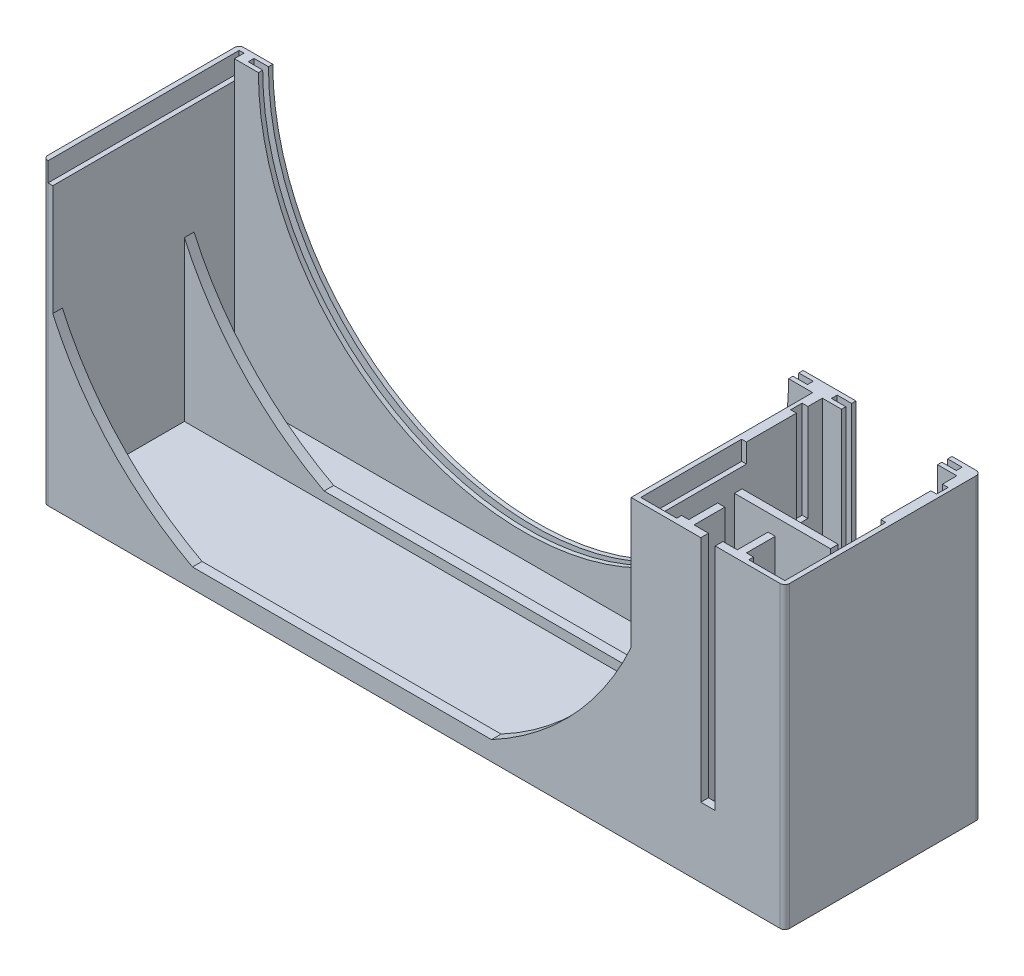
SolidWorks part; units mm, degrees
ref_plane "Plan de face" through (0, 0, 0) normal (0, 0, 1) x (1, 0, 0)
ref_plane "Plan de dessus" through (0, 0, 0) normal (0, 1, 0) x (1, 0, 0)
ref_plane "Plan de droite" through (0, 0, 0) normal (1, 0, 0) x (0, 0, -1)
sketch "Esquisse1" plane through (0, 0, 0) normal (0, 1, 0) x (1, 0, 0)
  line L1 (0, 0) -> (154.4, 0)
  line L2 (0, 0) -> (0, 40.8)
  line L3 (0, 40.8) -> (154.4, 40.8)
  line L4 (154.4, 0) -> (154.4, 40.8)
  dimension "D1" = 154.4
  dimension "D2" = 40.8
extrude "Boss.-Extru.1" add sketch "Esquisse1" along normal blind 2
sketch "Esquisse2" plane through (0, 2, 0) normal (0, 1, 0) x (1, 0, 0)
  line L0 (2, 37.8) -> (2, 29.4)
  line L1 (0, 40.8) -> (154.4, 40.8)
  line L2 (0, 40.8) -> (0, 0)
  line L3 (0, 0) -> (154.4, 0)
  line L4 (154.4, 40.8) -> (154.4, 0)
  line L5 (2, 2) -> (122.4, 2)
  line L8 (124.4, 37.8) -> (124.4, 2)
  line L10 (122.4, 37.8) -> (122.4, 29.4)
  line L22 (152.4, 37.8) -> (152.4, 2)
  line L23 (2, 38.8) -> (152.4, 38.8) construction
  line L24 (124.4, 2) -> (132.4, 2)
  line L25 (152.4, 38.8) -> (152.4, 2) construction
  line L26 (144.4, 2) -> (152.4, 2)
  line L27 (2, 2) -> (152.4, 2) construction
  line L29 (132.4, 2) -> (132.4, 8)
  line L30 (132.4, 8) -> (144.4, 8)
  line L31 (144.4, 2) -> (144.4, 8)
  line L32 (2, 27.4) -> (2, 2)
  line L33 (2, 29.4) -> (122.4, 29.4)
  line L35 (2, 27.4) -> (122.4, 27.4)
  line L37 (122.4, 27.4) -> (122.4, 2)
  line L38 (2, 38.8) -> (2, 2) construction
  line L39 (122.4, 37.8) -> (2, 37.8)
  line L40 (152.4, 37.8) -> (124.4, 37.8)
  dimension "D2" = 2
  dimension "D3" = 120.4
  dimension "D4" = 12
  dimension "D5" = 6
  dimension "D6" = 8
  dimension "D7" = 2
  dimension "D8" = 25.4
  dimension "D9" = 3
  dimension "D11" = 3
  dimension "D1" = 2
extrude "Boss.-Extru.2" add sketch "Esquisse2" along normal blind 60.2
sketch "Esquisse3" plane through (0, 0, 0) normal (0, 0, 1) x (1, 0, 0)
  line L3 (2, 62.2) -> (122.4, 62.2)
  line L4 (2, 62.2) -> (2, 35.1452)
  line L5 (31.0751, 4) -> (93.3249, 4)
  line L6 (122.4, 62.2) -> (122.4, 35.1452)
  line L7 (0, 62.2) -> (0, 0) construction
  line L8 (0, 0) -> (154.4, 0) construction
  line L9 (0, 62.2) -> (154.4, 62.2) construction
  arc A0 (2, 35.1452) -> (31.0751, 4) centre (62.2, 62.2) ccw
  arc A1 (93.3249, 4) -> (122.4, 35.1452) centre (62.2, 62.2) ccw
  dimension "D1" = 132
  dimension "D2" = 2
  dimension "D3" = 4
  dimension "D4" = 120.4
extrude "Enlèv. mat.-Extru.1" cut sketch "Esquisse3" against normal up to surface (29.4 mm away) up to face at (62.2, 32.1, -29.4)
sketch "Esquisse15" plane through (0, 0, -40.8) normal (0, 0, -1) x (-1, 0, 0)
  line L0 (-154.4, 62.2) -> (-122.4, 62.2) construction
  line L1 (-148.4, 62.2) -> (-128.4, 62.2)
  line L2 (-148.4, 62.2) -> (-148.4, 15)
  line L3 (-148.4, 15) -> (-128.4, 15)
  line L4 (-128.4, 62.2) -> (-128.4, 15)
  line L5 (-154.4, 62.2) -> (0, 62.2) construction
  line L6 (-154.4, 62.2) -> (-154.4, 0) construction
  line L7 (-154.4, 0) -> (0, 0) construction
  point P9 (-138.4, 62.2)
  point P10 (-138.4, 62.2)
  dimension "D1" = 32
  dimension "D2" = 6
  dimension "D3" = 15
sketch "Esquisse4" plane through (0, 62.2, 0) normal (0, 1, 0) x (1, 0, 0)
  line L0 (2, 0) -> (1, 0)
  line L10 (130.9, 1) -> (130.9, 2)
  line L12 (124.4, 2) -> (124.4, 22)
  line L13 (124.4, 22) -> (123.4, 22)
  line L14 (123.4, 2) -> (123.4, 22)
  line L16 (152.4, 2) -> (152.4, 22)
  line L17 (152.4, 22) -> (153.4, 22)
  line L18 (153.4, 2) -> (153.4, 22)
  line L19 (124.4, 2) -> (130.9, 2)
  line L20 (123.4, 2) -> (123.4, 1)
  line L21 (123.4, 1) -> (130.9, 1)
  line L22 (153.4, 2) -> (153.4, 1)
  line L23 (130.9, 1.5) -> (145.9, 1.5) construction
  line L24 (145.9, 1) -> (145.9, 2)
  line L25 (145.9, 2) -> (152.4, 2)
  line L26 (145.9, 1) -> (153.4, 1)
  line L27 (152.4, 2) -> (152.4, 37.8) construction
  line L28 (0, 0) -> (2, 0) construction
  line L29 (1, 0) -> (1, 39.8)
  line L31 (2, 39.8) -> (1, 39.8)
  line L33 (154.4, 40.8) -> (0, 40.8) construction
  line L38 (2, 39.8) -> (2, 0)
  point P29 (145.9, 1.5)
  dimension "D1" = 1
  dimension "D2" = 1
  dimension "D5" = 1
  dimension "D6" = 21
  dimension "D8" = 15
  dimension "D9" = 7.5
extrude "Enlèv. mat.-Extru.2" cut sketch "Esquisse4" against normal blind 4
sketch "Esquisse5" plane through (0, 62.2, 0) normal (0, 1, 0) x (1, 0, 0)
  line L0 (124.4, 37.8) -> (124.4, 22) construction
  line L1 (124.4, 32.4) -> (123.2, 32.4)
  line L2 (124.4, 32.4) -> (124.4, 34.8)
  line L3 (124.4, 34.8) -> (123.2, 34.8)
  line L4 (123.2, 32.4) -> (123.2, 34.8)
  line L5 (152.4, 37.8) -> (124.4, 37.8) construction
  line L6 (153.6, 32.4) -> (153.6, 34.8)
  line L13 (124.4, 37.8) -> (152.4, 37.8) construction
  line L15 (152.4, 22) -> (152.4, 37.8) construction
  line L16 (138.4, 37.8) -> (138.4, 0) construction
  line L17 (122.4, 0) -> (154.4, 0) construction
  line L18 (152.4, 34.8) -> (153.6, 34.8)
  line L19 (152.4, 32.4) -> (152.4, 34.8)
  line L20 (152.4, 32.4) -> (153.6, 32.4)
  dimension "D1" = 3
  dimension "D2" = 2.4
  dimension "D3" = 1.2
extrude "Enlèv. mat.-Extru.3" cut sketch "Esquisse5" against normal offset from surface (20.2 mm away) 40 up to face at (138.4, 2, -12.45)
sketch "Esquisse6" plane through (0, 2, 0) normal (0, 1, 0) x (1, 0, 0)
  line L11 (152.4, 37.8) -> (133, 37.8)
  line L12 (152.4, 37.8) -> (152.4, 22.4)
  line L13 (152.4, 22.4) -> (133, 22.4)
  line L14 (133, 37.8) -> (133, 22.4)
  line L15 (152.4, 37.8) -> (131.8, 37.8)
  line L16 (152.4, 37.8) -> (152.4, 21.2)
  line L17 (152.4, 21.2) -> (131.8, 21.2)
  line L18 (131.8, 37.8) -> (131.8, 21.2)
  dimension "D1" = 15.4
  dimension "D2" = 19.4
  dimension "D3" = 1.2
  dimension "D4" = 1.2
extrude "Boss.-Extru.3" add sketch "Esquisse6" along normal blind 8
sketch "Esquisse9" plane through (0, 0, -8) normal (0, 0, -1) x (-1, 0, 0)
  line L0 (-132.4, 2) -> (-144.4, 2) construction
  line L1 (-133.9, 62.2) -> (-142.9, 62.2)
  line L2 (-133.9, 62.2) -> (-133.9, 10.5)
  line L3 (-133.9, 10.5) -> (-142.9, 10.5)
  line L4 (-142.9, 62.2) -> (-142.9, 10.5)
  line L5 (-132.4, 62.2) -> (-144.4, 62.2) construction
  line L6 (-132.4, 2) -> (-144.4, 2) construction
  point P12 (-138.4, 10.5)
  point P13 (-138.4, 2)
  dimension "D1" = 8.5
  dimension "D2" = 9
extrude "Enlèv. mat.-Extru.5" cut sketch "Esquisse9" against normal blind 6.4
sketch "Esquisse10" plane through (0, 0, -1.6) normal (0, 0, -1) x (-1, 0, 0)
  line L0 (-142.9, 10.5) -> (-133.9, 10.5) construction
  line L1 (-136.9, 62.2) -> (-139.9, 62.2)
  line L2 (-136.9, 62.2) -> (-136.9, 14.5)
  line L3 (-136.9, 14.5) -> (-139.9, 14.5)
  line L4 (-139.9, 62.2) -> (-139.9, 14.5)
  line L5 (-133.9, 62.2) -> (-142.9, 62.2) construction
  line L6 (-133.9, 62.2) -> (-142.9, 62.2) construction
  point P12 (-138.4, 62.2)
  point P13 (-138.4, 14.5)
  dimension "D1" = 3
  dimension "D2" = 4
extrude "Enlèv. mat.-Extru.6" cut sketch "Esquisse10" against normal through all
sketch "Esquisse11" plane through (0, 2, 0) normal (0, 1, 0) x (1, 0, 0)
  line L0 (132.4, 8) -> (144.4, 8) construction
  line L1 (132.4, 13.1) -> (152.4, 13.1)
  line L2 (132.4, 13.1) -> (132.4, 11.5)
  line L3 (132.4, 11.5) -> (152.4, 11.5)
  line L4 (152.4, 13.1) -> (152.4, 11.5)
  line L5 (132.4, 2) -> (132.4, 8) construction
  line L6 (152.4, 2) -> (152.4, 21.2) construction
  dimension "D1" = 3.5
  dimension "D2" = 1.6
extrude "Boss.-Extru.4" add sketch "Esquisse11" along normal up to surface (60.2 mm away) up to face at (118.7714, 62.2, -17.1333)
sketch "Esquisse12" plane through (0, 0, -40.8) normal (0, 0, -1) x (-1, 0, 0)
  line L0 (-154.4, 62.2) -> (0, 62.2) construction
  line L1 (-124.4, 62.2) -> (0, 62.2) construction
  circle A0 centre (-62.2, 62.2) radius 55.2
  point P7 (-62.2, 62.2)
  dimension "D1" = 110.4
  dimension "D2" = 124.4
extrude "Enlèv. mat.-Extru.7" cut sketch "Esquisse12" against normal up to next
sketch "Esquisse14" plane through (0, 0, -40.8) normal (0, 0, -1) x (-1, 0, 0)
  circle A0 centre (-62.2, 62.2) radius 58.2
  arc A1 (-117.4, 62.2) -> (-7, 62.2) centre (-62.2, 62.2) ccw construction
  dimension "D1" = 3
extrude "Enlèv. mat.-Extru.8" cut sketch "Esquisse14" against normal blind 1.2 from offset 0.9 offset against normal yes
fillet "Congé1" radius 1 4 edges at (154.4, 31.1, 0) (154.4, 31.1, -40.8) (0, 31.1, 0) (0, 31.1, -40.8)
extrude "Enlèv. mat.-Extru.9" cut sketch "Esquisse15" against normal up to next
sketch "Esquisse16" plane through (0, 0, -40.8) normal (0, 0, -1) x (-1, 0, 0)
  line L0 (-151.4, 65.2) -> (-151.4, 12)
  line L1 (-148.4, 62.2) -> (-128.4, 62.2)
  line L2 (-148.4, 62.2) -> (-148.4, 15)
  line L3 (-148.4, 15) -> (-128.4, 15)
  line L4 (-128.4, 62.2) -> (-128.4, 15)
  line L5 (-151.4, 12) -> (-125.4, 12)
  line L6 (-125.4, 65.2) -> (-125.4, 12)
  line L7 (-151.4, 65.2) -> (-125.4, 65.2)
  dimension "D1" = 3
extrude "Enlèv. mat.-Extru.11" cut sketch "Esquisse16" against normal blind 1.2 from offset 0.9 offset against normal yes
